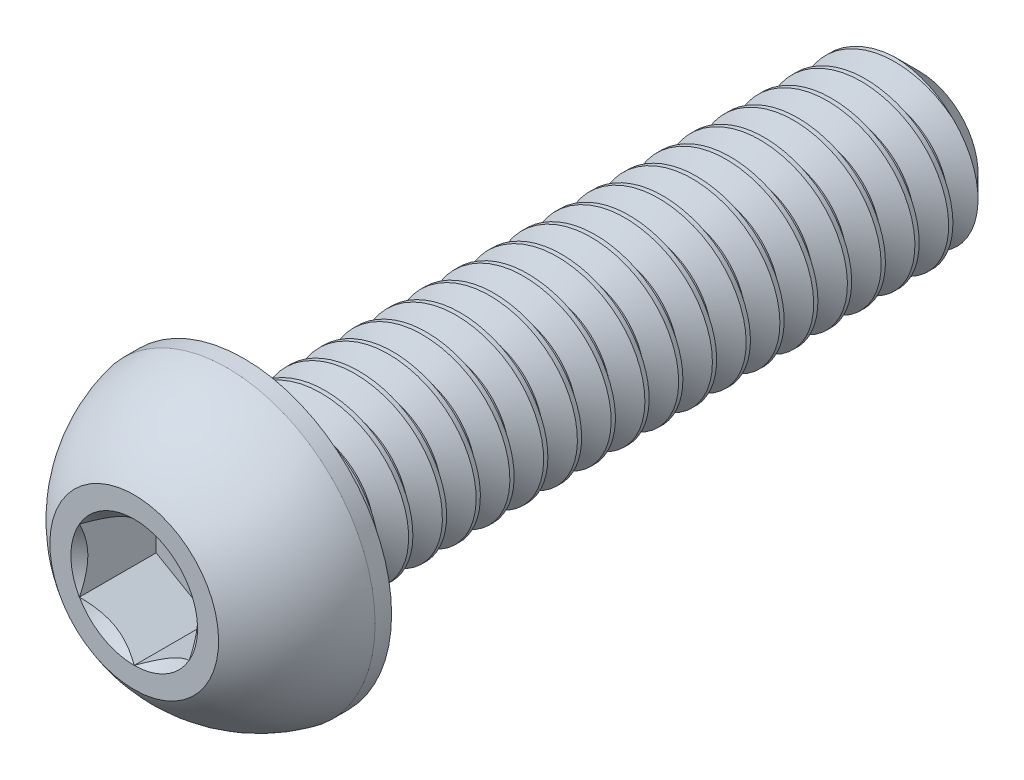
SolidWorks part; units mm, degrees
note: '?' marks a value the reader was unsure of.
material "18-8 Stainless Steel"
ref_plane "Front" through (0, 0, 0) normal (0, 0, 1) x (1, 0, 0)
ref_plane "Top" through (0, 0, 0) normal (0, 1, 0) x (1, 0, 0)
ref_plane "Right" through (0, 0, 0) normal (1, 0, 0) x (0, 0, -1)
sketch "Sketch1" plane through (0, 0, 0) normal (1, 0, 0) x (0, 0, -1)
  line L2 (1.3, 1) -> (9.3, 1)
  line L3 (9.3, 1) -> (9.3, 0)
  line L4 (9.3, 0) -> (1.3, 0)
  line L6 (1.105, 1.75) -> (1.3, 1.75) construction
  line L7 (9.3, 1) -> (9.3, -1) construction
  line L8 (0, 0) -> (1.3, 0) construction
  line L9 (1.3, 1.75) -> (1.3, -1.75) construction
  line L11 (1.3, 1) -> (1.3, 0)
  line L13 (0, 0.65) -> (0, -0.65) construction
  line L14 (0, 0.65) -> (0, 1) construction
  arc A3 (0, 1) -> (1.105, 1.75) centre (1.4858, 0) cw construction
  dimension "D1" = 0.195
revolve "Revolve1" add sketch "Sketch1" angle 360 mid plane about L4
sketch "Sketch3" plane through (0, 0, -9.3) normal (0, 0, -1) x (-1, 0, 0)
  circle A0 centre (0, 0) radius 1
curve "Helix/Spiral1" pitch 0.4 height 8.4 turns 21
chamfer "Chamfer1" distance 0.3 angle 45 1 edges at (0, 1, -9.3)
sketch "Sketch7" plane through (0, 0, 0) normal (1, 0, 0) x (0, 0, -1)
  line L6 (1.105, 1.75) -> (1.3, 1.75) construction
  line L8 (0, 0) -> (1.3, 0) construction
  line L11 (1.3, 1.75) -> (1.3, -1.75) construction
  line L12 (1.105, 1.75) -> (1.3, 1.75)
  line L13 (0, 0) -> (1.3, 0)
  line L14 (0, 0.65) -> (0, -0.65) construction
  line L15 (1.3, 1.75) -> (1.3, 0)
  line L16 (0, 1) -> (0, 0)
  arc A2 (1.105, 1.75) -> (0, 1) centre (1.4858, 0) ccw construction
  arc A3 (1.105, 1.75) -> (0, 1) centre (1.4858, 0) ccw
revolve "Revolve2" add sketch "Sketch7" angle 360 mid plane about L13
sketch "Sketch5" plane through (0, 0, 0) normal (0, 0, 1) x (1, 0, 0)
  line L1 (0.65, -0.3753) -> (0.65, 0.3753)
  line L2 (0.65, 0.3753) -> (0, 0.7506)
  line L3 (0, 0.7506) -> (-0.65, 0.3753)
  line L4 (-0.65, 0.3753) -> (-0.65, -0.3753)
  line L5 (-0.65, -0.3753) -> (0, -0.7506)
  line L6 (0, -0.7506) -> (0.65, -0.3753)
  circle A0 centre (0, 0) radius 0.65 construction
extrude "Cut-Extrude2" cut sketch "Sketch5" against normal blind 0.91
sketch "Sketch6" plane through (0, 0, 0) normal (0, 0, 1) x (1, 0, 0)
  circle A0 centre (0, 0) radius 0.7506
extrude "Cut-Extrude3" cut sketch "Sketch6" against normal blind 0.91 draft 45
sketch "Sketch2" plane through (0, 0, 0) normal (1, 0, 0) x (0, 0, -1)
  line L0 (9, 1) -> (9.35, 1)
  line L1 (9.35, 1) -> (9.2, 0.7402)
  line L2 (9.2, 0.7402) -> (9.15, 0.7402)
  line L3 (9.15, 0.7402) -> (9, 1)
  line L4 (9.075, 0.8701) -> (9.275, 0.8701) construction
  dimension "D1" = 60
  dimension "D2" = 0.05
  dimension "D3" = 0.2
sweep "Cut-Sweep1" cut profiles "Sketch2" path "Helix/Spiral1"
sketch "Sketch10" plane through (0, 0, 0) normal (1, 0, 0) x (0, 0, -1)
  line L0 (9.3, 1) -> (9.3, -1) construction
  point P0 (8.7, -1)
  dimension "D1" = 0.6
ref_axis "Center Axis 1" through (0, 0, -8.1113) along (0, 0, 1)?
ref_plane "Contact Plane 1" through (0, 0, -1.3) normal (0, 0, -1) x (-1, 0, 0)
ref_plane "Contact Plane 2" through (0, 0, 0) normal (0, 0, 1) x (1, 0, 0)
equation "\"D3@Helix/Spiral1\" = \"Lg@Sketch1\" + \"D4@Helix/Spiral1\""
equation "\"D2@Sketch2\" = \"D4@Helix/Spiral1\" * .125"
equation "\"D3@Sketch2\" = \"D4@Helix/Spiral1\" * .5"
equation "\"D1@Chamfer1\" = \"D4@Helix/Spiral1\" * .75"
equation "\"D1@Cut-Extrude2\" = \"Head Ht@Sketch1\" * .7"
equation "\"D1@Sketch1\" = \"Head Ht@Sketch1\" * .15"
equation "\"D1@Sketch10\" = \"D4@Helix/Spiral1\" * 1.5"
equation "\"D1@Cut-Extrude3\" = \"D1@Cut-Extrude2\""
